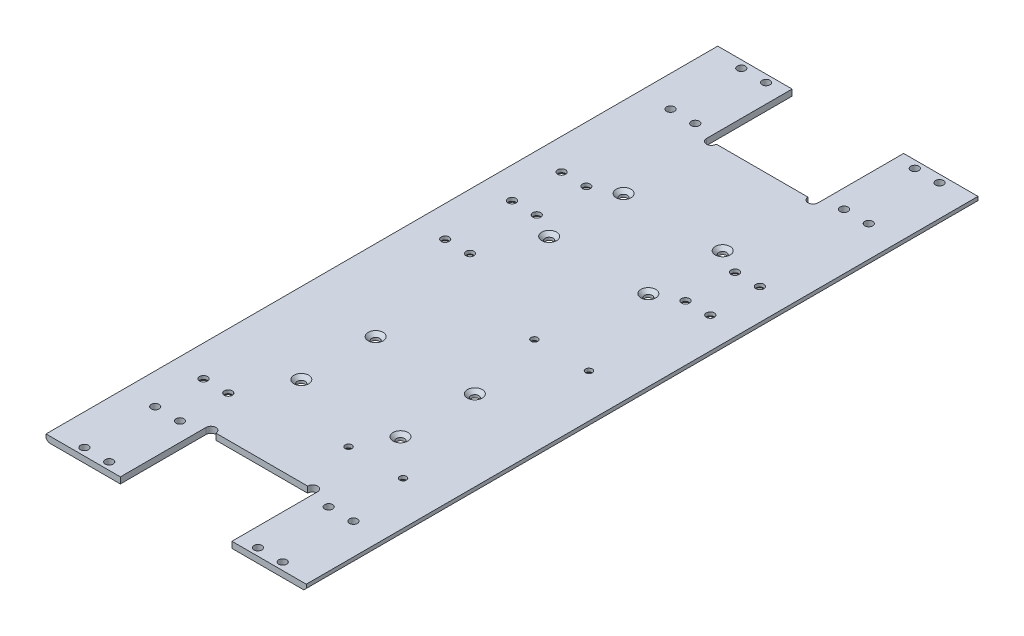
SolidWorks part; units mm, degrees
ref_plane "前视基准面" through (0, 0, 0) normal (0, 0, 1) x (1, 0, 0)
ref_plane "上视基准面" through (0, 0, 0) normal (0, 1, 0) x (1, 0, 0)
ref_plane "右视基准面" through (0, 0, 0) normal (1, 0, 0) x (0, 0, -1)
sketch "草图1" plane through (0, 0, 0) normal (0, 1, 0) x (1, 0, 0)
  line L6 (-52.5, -135.5) -> (52.5, -135.5)
  line L7 (52.5, -135.5) -> (52.5, 135.5)
  line L8 (-52.5, 135.5) -> (52.5, 135.5)
  line L9 (-52.5, -135.5) -> (-52.5, 135.5)
  point P8 (-50, 0)
extrude "凸台-拉伸1" add sketch "草图1" along normal blind 2.5
sketch "草图2" plane through (0, 2.5, 0) normal (0, 1, 0) x (1, 0, 0)
  circle A14 centre (35, -3.95) radius 1.35
  circle A15 centre (13, -3.95) radius 1.35
  circle A18 centre (35, -78.95) radius 1.35
  circle A19 centre (13, -78.95) radius 1.35
  circle A32 centre (20, -35) radius 1.6
  circle A33 centre (-20, -35) radius 1.6
  circle A34 centre (20, -65) radius 1.6
  circle A35 centre (-20, -65) radius 1.6
  circle A36 centre (-20, 35) radius 1.6
  circle A37 centre (20, 35) radius 1.6
  circle A40 centre (-20, 65) radius 1.6
  circle A41 centre (20, 65) radius 1.6
extrude "切除-拉伸1" cut sketch "草图2" against normal blind 10
sketch "草图7" plane through (0, 2.5, 0) normal (0, 1, 0) x (1, 0, 0)
  line L0 (0, -1.375) -> (0, 1.375) construction
  circle A0 centre (-40, 60) radius 1.6
  circle A1 centre (-30, 60) radius 1.6
  circle A2 centre (30, 60) radius 1.6
  circle A3 centre (40, 60) radius 1.6
  circle A4 centre (-40, 40) radius 1.6
  circle A5 centre (-30, 40) radius 1.6
  circle A6 centre (30, 40) radius 1.6
  circle A7 centre (40, 40) radius 1.6
  dimension "D1" = 2
chamfer "倒角4" distance 1.4 angle 45 8 edges at (-20, 2.5, 63.4) (-20, 2.5, 33.4) (20, 2.5, 66.6) (20, 2.5, 36.6) (-20, 2.5, -33.4) (-20, 2.5, -63.4) (20, 2.5, -36.6) (20, 2.5, -66.6)
chamfer "倒角5" distance 1 angle 45 2 edges at (52.5, 0, 0) (-52.5, 0, 0)
sketch "草图4" plane through (0, 0, 0) normal (0, -1, 0) x (1, 0, 0)
  line L0 (1.375, 0) -> (-1.375, 0) construction
  line L1 (-51.5, 135.5) -> (51.5, 135.5) construction
  line L2 (0, 100.95) -> (22.5, 100.95)
  line L3 (22.5, 100.95) -> (22.5, 135.5)
  line L4 (22.5, 135.5) -> (-22.5, 135.5)
  line L5 (-22.5, 135.5) -> (-22.5, 100.95)
  line L6 (-22.5, 100.95) -> (0, 100.95)
  line L7 (-22.5, -100.95) -> (0, -100.95)
  line L8 (-22.5, -135.5) -> (-22.5, -100.95)
  line L9 (22.5, -135.5) -> (-22.5, -135.5)
  line L10 (22.5, -100.95) -> (22.5, -135.5)
  line L11 (0, -100.95) -> (22.5, -100.95)
extrude "切除-拉伸2" cut sketch "草图4" against normal blind 10
sketch "草图6" plane through (0, 0, 0) normal (0, -1, 0) x (1, 0, 0)
  line L0 (0, -1.375) -> (0, 1.375) construction
  line L2 (1.375, 0) -> (-1.375, 0) construction
  circle A0 centre (-40, 132.5) radius 1.6
  circle A1 centre (-30, 132.5) radius 1.6
  circle A2 centre (-30, 103.95) radius 1.6
  circle A3 centre (-40, 103.95) radius 1.6
  circle A4 centre (40, 103.95) radius 1.6
  circle A5 centre (30, 103.95) radius 1.6
  circle A6 centre (30, 132.5) radius 1.6
  circle A7 centre (40, 132.5) radius 1.6
  circle A8 centre (40, -132.5) radius 1.6
  circle A9 centre (30, -132.5) radius 1.6
  circle A10 centre (30, -103.95) radius 1.6
  circle A11 centre (40, -103.95) radius 1.6
  circle A12 centre (-40, -103.95) radius 1.6
  circle A13 centre (-30, -103.95) radius 1.6
  circle A14 centre (-30, -132.5) radius 1.6
  circle A15 centre (-40, -132.5) radius 1.6
extrude "切除-拉伸3" cut sketch "草图6" against normal blind 10
extrude "切除-拉伸4" cut sketch "草图7" against normal blind 10
sketch "草图8" plane through (0, 0, 0) normal (0, -1, 0) x (1, 0, 0)
  line L4 (-40, 132.5) -> (-30, 132.5)
  circle A1 centre (-40, 84.45) radius 1.6
  circle A2 centre (-30, 84.45) radius 1.6
  circle A3 centre (-40, -13.05) radius 1.6
  circle A4 centre (-30, -13.05) radius 1.6
extrude "切除-拉伸5" cut sketch "草图8" against normal blind 10 contours A1 | A2 | A4 | A3 region at (-40, 0, 84.45)
sketch "草图9" plane through (0, 0, 0) normal (0, -1, 0) x (1, 0, 0)
  line L0 (0, -1.375) -> (0, 1.375) construction
  line L1 (1.375, 0) -> (-1.375, 0) construction
  line L2 (-22.5, 100.95) -> (22.5, 100.95) construction
  circle A3 centre (20.5, 100.95) radius 2
  circle A4 centre (-20.5, 100.95) radius 2
  circle A5 centre (-20.5, -100.95) radius 2
  circle A6 centre (20.5, -100.95) radius 2
extrude "切除-拉伸6" cut sketch "草图9" against normal blind 10
chamfer "倒角3" distance 1.15 angle 45 16 edges at (13, 0, 2.6) (35, 0, 2.6) (35, 0, 77.6) (13, 0, 77.6) (40, 0, -61.6) (30, 0, -61.6) (-30, 0, -61.6) (-40, 0, -61.6) (-30, 0, -14.65) (-40, 0, -14.65) (-30, 0, 82.85) (-40, 0, 82.85) (-40, 0, -41.6) (-30, 0, -41.6) (30, 0, -41.6) (40, 0, -41.6)
